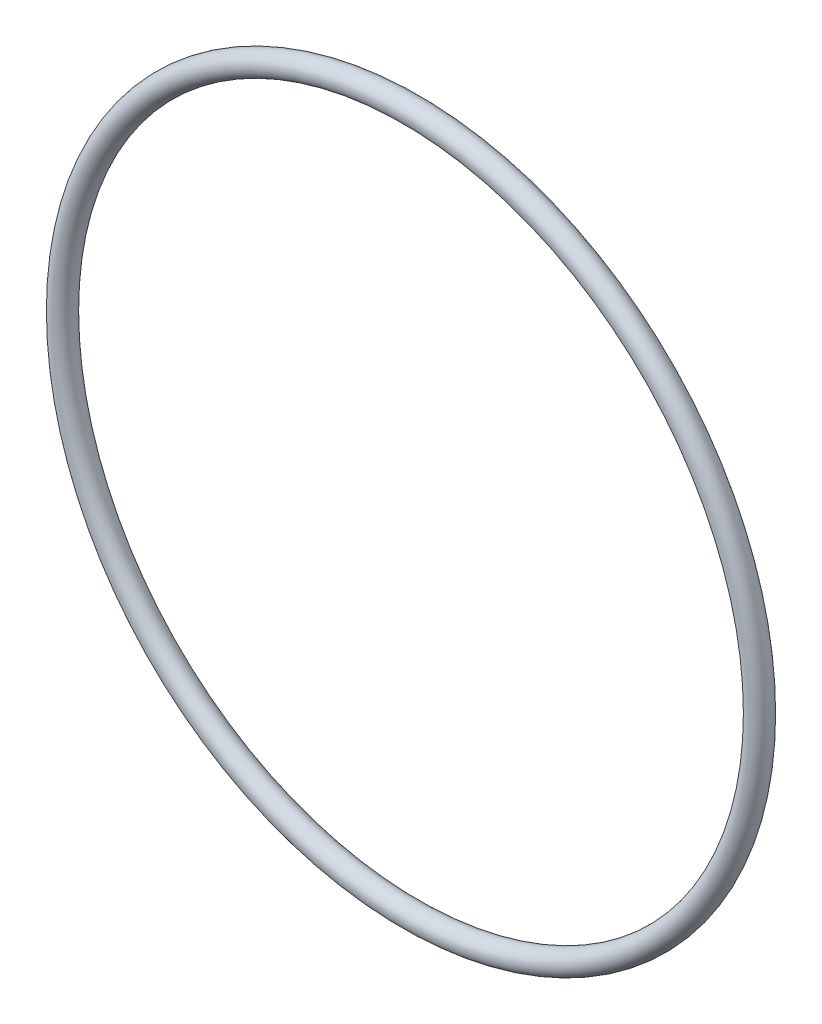
SolidWorks part; units mm, degrees
ref_plane "Front Plane" through (0, 0, 0) normal (0, 0, 1) x (1, 0, 0)
ref_plane "Top Plane" through (0, 0, 0) normal (0, 1, 0) x (1, 0, 0)
ref_plane "Right Plane" through (0, 0, 0) normal (1, 0, 0) x (0, 0, -1)
sketch "Sketch1" plane through (0, 0, 0) normal (0, 0, 1) x (1, 0, 0)
  line L0 (-55.7149, 0) -> (55.7149, 0) construction
  line L1 (-52.1843, 0) -> (52.1843, 0) construction
  line L2 (-39.3964, 39.3964) -> (39.3964, -39.3964) construction
  point P3 (52.1843, 0)
  point P4 (0, 0)
  point P8 (0, 0)
  point P9 (0, 0)
  point P10 (-55.7149, 0)
  point P11 (-52.1843, 0)
  point P14 (0, 0)
  point P15 (39.3964, -39.3964)
  point P16 (55.7149, 0)
  dimension "Actual OD" = 111.4298
  dimension "Actual ID" = 104.3686
  dimension "Actual Width" = 3.5306
  dimension "D1" = 45
sketch "Sketch2" plane through (0, 0, 0) normal (0, 1, 0) x (1, 0, 0)
  line L0 (-55.7149, 0) -> (55.7149, 0) construction
  line L1 (-53.9496, 1.7653) -> (-53.9496, -1.7653) construction
  line L2 (0, -1.7653) -> (0, 1.7653) construction
  circle A0 centre (-53.9496, 0) radius 1.7653
  point P12 (0, 0)
revolve "Revolve1" add sketch "Sketch2" angle 360 about L2
sketch "Sketch3" plane through (0, 0, 0) normal (1, 0, 0) x (0, 0, -1)
  line L0 (-1.7653, 0) -> (1.7653, 0) construction
  line L1 (-1.7653, -39.1382) -> (-1.7653, 39.1382) construction
  point P4 (0, 0)
  point P7 (-1.7653, 0)
  point P9 (-1.7653, -39.1382)
  dimension "D1" = 3.5306
  dimension "D2" = 78.2764
ref_axis "Axis1" through (0, 0, -1.9418) along (0, 0, 1)
equation "\"D1@Sketch3\"=\"Actual Width@Sketch1\""
equation "\"D2@Sketch3\"=\"Actual ID@Sketch1\"*.75"
